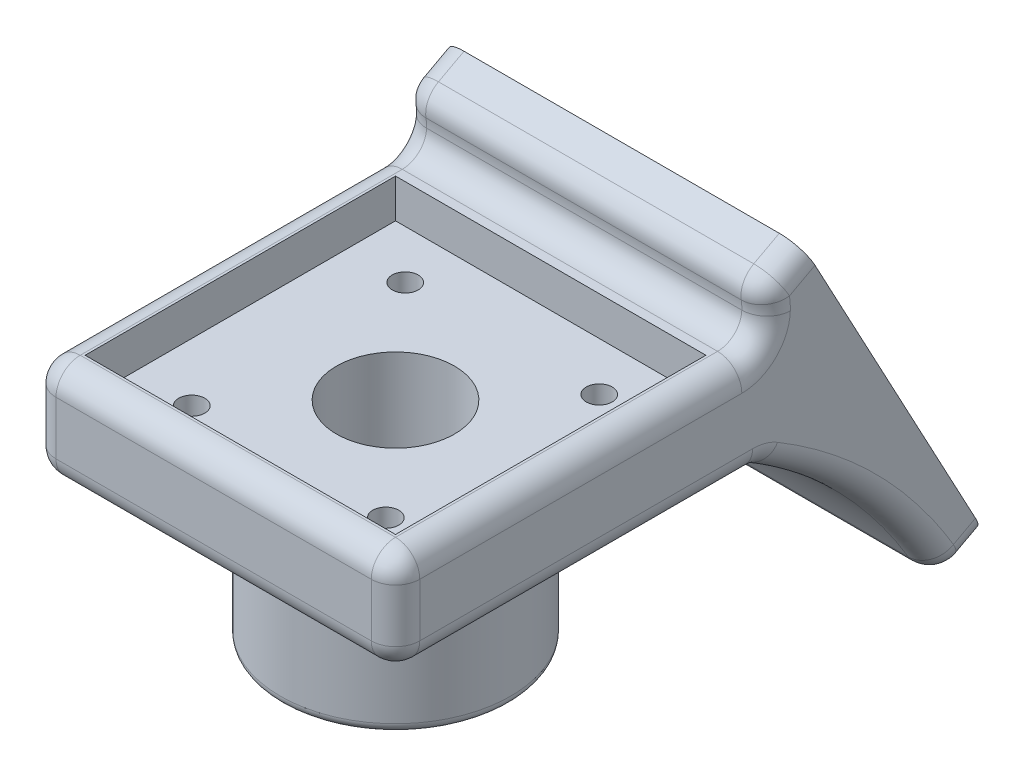
SolidWorks part; units mm, degrees
ref_plane "Front Plane" through (0, 0, 0) normal (0, 0, 1) x (1, 0, 0)
ref_plane "Top Plane" through (0, 0, 0) normal (0, 1, 0) x (1, 0, 0)
ref_plane "Right Plane" through (0, 0, 0) normal (1, 0, 0) x (0, 0, -1)
sketch "Sketch1" plane through (0, 0, 0) normal (0, 1, 0) x (1, 0, 0)
  line L13 (0, 0) -> (47.625, 0)
  line L14 (0, 0) -> (0, 47.625)
  line L15 (0, 47.625) -> (47.625, 47.625)
  line L16 (47.625, 0) -> (47.625, 47.625)
  dimension "D1" = 47.625
extrude "Boss-Extrude1" add sketch "Sketch1" along normal blind 13.335
sketch "Sketch2" plane through (0, 13.335, 0) normal (0, 1, 0) x (1, 0, 0)
  line L0 (47.625, 47.625) -> (0, 47.625) construction
  line L1 (3.4925, 3.4925) -> (44.1325, 3.4925)
  line L2 (3.4925, 3.4925) -> (3.4925, 44.1325)
  line L3 (3.4925, 44.1325) -> (44.1325, 44.1325)
  line L4 (44.1325, 3.4925) -> (44.1325, 44.1325)
  line L5 (0, 47.625) -> (0, 0) construction
  point P6 (23.8125, 47.625)
  point P7 (23.8125, 44.1325)
  point P10 (0, 23.8125)
  point P11 (3.4925, 23.8125)
  dimension "D1" = 40.64
extrude "Cut-Extrude1" cut sketch "Sketch2" against normal blind 5.08
sketch "Sketch3" plane through (0, 0, 0) normal (0, -1, 0) x (1, 0, 0)
  line L0 (0, 0) -> (47.625, 0) construction
  line L1 (0, -47.625) -> (0, 0) construction
  circle A0 centre (23.8125, -23.8125) radius 15.0812
  point P3 (23.8125, -23.8125)
  point P4 (24.6106, -21.7055)
  point P7 (23.8125, 0)
  point P10 (0, -23.8125)
  dimension "D1" = 30.1625
extrude "Boss-Extrude2" add sketch "Sketch3" along normal blind 19.05
sketch "Sketch4" plane through (0, -19.05, 0) normal (0, -1, 0) x (1, 0, 0)
  line L0 (11.1125, -9.8425) -> (36.5125, -9.8425) construction
  line L1 (36.5125, -9.8425) -> (36.5125, -37.7825) construction
  line L2 (36.5125, -37.7825) -> (11.1125, -37.7825) construction
  line L3 (11.1125, -37.7825) -> (11.1125, -9.8425) construction
  circle A0 centre (23.8125, -23.8125) radius 7.7216
  circle A1 centre (11.1125, -9.8425) radius 1.7018
  circle A2 centre (36.5125, -9.8425) radius 1.7018
  circle A3 centre (36.5125, -37.7825) radius 1.7018
  circle A4 centre (11.1125, -37.7825) radius 1.7018
  point P11 (11.1386, -10.979)
  point P12 (23.8125, -9.8425)
  point P13 (0, 0)
  point P14 (11.1125, -23.8125)
  dimension "D1" = 15.4432
  dimension "D2" = 3.4036
  dimension "D3" = 25.4
  dimension "D4" = 27.94
extrude "Cut-Extrude2" cut sketch "Sketch4" against normal up to surface (32.385 mm away) up to face at (23.8125, 13.335, -23.8125)
fillet "Fillet2" radius 1.27 2 edges at (23.8125, -19.05, -31.5341) (23.8125, -19.05, -38.8937)
fillet "Fillet3" radius 1.905 1 edges at (23.8125, 0, -38.8937)
sketch "Sketch6" plane through (47.625, 0, 0) normal (1, 0, 0) x (0, 0, -1)
  line L0 (71.83, -25.0883) -> (47.8245, 19.6819)
  line L2 (47.625, 13.335) -> (47.625, 0) construction
  line L4 (71.83, -25.0883) -> (77.4263, -22.0877)
  line L5 (77.4263, -22.0877) -> (53.4207, 22.6826)
  line L6 (53.4207, 22.6826) -> (47.8245, 19.6819)
  dimension "D1" = 28.2
  dimension "D2" = 6.35
  dimension "D3" = 50.8
  dimension "D4" = 6.35
  dimension "D5" = 3.175
extrude "Boss-Extrude3" add sketch "Sketch6" against normal up to surface (47.625 mm away) separate body up to face at (0, 6.6675, -23.8125)
sketch "Sketch10" plane through (47.625, 0, 0) normal (1, 0, 0) x (0, 0, -1)
  line L0 (47.625, 13.335) -> (47.625, 0) construction
  line L1 (47.625, 0) -> (47.625, 13.335)
  line L2 (47.8245, 19.6819) -> (71.83, -25.0883)
  line L3 (0, 13.335) -> (47.625, 13.335) construction
  spline S0 degree 2 poles (71.83, -25.0883) (63.0467, -8.9999) (47.625, 0) knots 0 0 0 1 1 1
  spline S1 degree 2 poles (47.625, 13.335) (49.3003, 16.2896) (47.8245, 19.6819) knots 0 0 0 1 1 1
  point P5 (47.625, 13.335)
  point P11 (47.6695, 14.7509)
  dimension "D1" = 6.604
  dimension "D2" = 35.306
extrude "Boss-Extrude4" add sketch "Sketch10" against normal up to surface (47.625 mm away) contours S1 L1 S0 L2 region at (47.625, 1.0569, -54.4112) up to face at (0, -1.2029, -62.6254)
fillet "Fillet7" radius 3.175 20 edges at (23.8125, 13.335, -47.625) (23.8125, 19.6819, -47.8245) (23.8125, 0, -47.625) (0, 13.335, -23.8125) (0, 0, -23.8125) (0, 6.6675, 0) (23.8125, 0, 0) (23.8125, 13.335, 0) (47.625, 6.6675, 0) (47.625, 13.335, -23.8125) (47.625, 0, -23.8125) (23.8125, -25.0883, -71.83) (0, -23.588, -74.6282) (47.625, -23.588, -74.6282) (0, 21.1822, -50.6226) (47.625, 21.1822, -50.6226)
